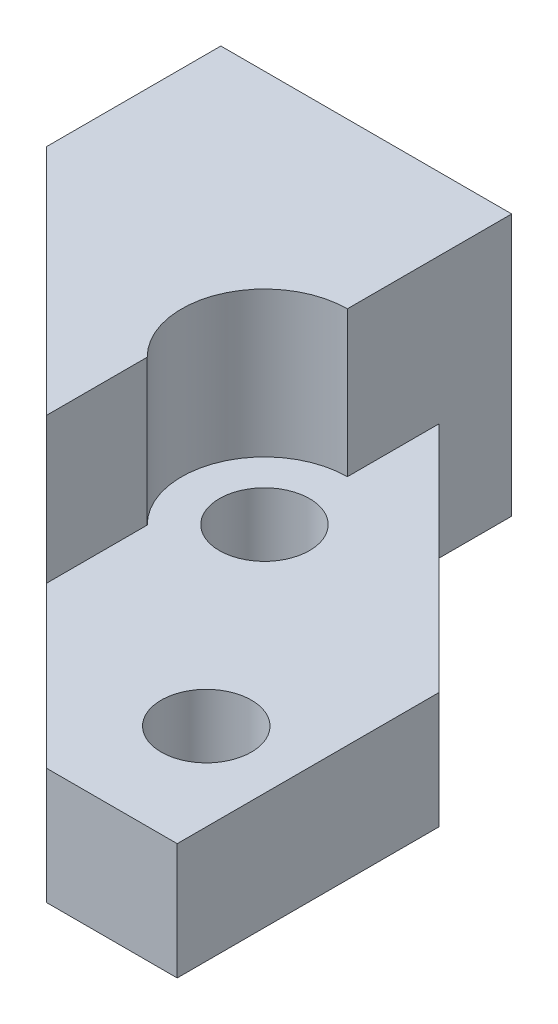
SolidWorks part; units mm, degrees
ref_plane "前视基准面" through (0, 0, 0) normal (0, 0, 1) x (1, 0, 0)
ref_plane "上视基准面" through (0, 0, 0) normal (0, 1, 0) x (1, 0, 0)
ref_plane "右视基准面" through (0, 0, 0) normal (1, 0, 0) x (0, 0, -1)
other "Configuration Table"
sketch "草图1" plane through (0, 0, 0) normal (0, 1, 0) x (1, 0, 0)
  line L1 (0, 0) -> (10, 0)
  line L2 (0, 0) -> (0, 15)
  line L3 (0, 15) -> (10, 15)
  line L4 (10, 0) -> (10, 15)
  circle A0 centre (7, 4) radius 1.55
  circle A1 centre (2, 11) radius 1.55
  dimension "D3" = 7
  dimension "D4" = 5
  dimension "D5" = 3.1
  dimension "D6" = 3.1
  dimension "D8" = 3
  dimension "D1" = 10
  dimension "D2" = 15
  dimension "D7" = 4
extrude "凸台-拉伸1" add sketch "草图1" along normal blind 4
sketch "草图2" plane through (0, 0, 0) normal (-1, 0, 0) x (0, 0, 1)
  line L1 (-5, 9) -> (-19.5, 9)
  line L2 (-5, 9) -> (-5, 0)
  line L3 (-5, 0) -> (-19.5, 0)
  line L4 (-19.5, 9) -> (-19.5, 0)
  line L5 (0, 4) -> (0, 0) construction
  line L6 (-15, 0) -> (0, 0) construction
  dimension "D1" = 5
  dimension "D2" = 14.5
  dimension "D3" = 9
  dimension "D4" = 0
extrude "凸台-拉伸2" add sketch "草图2" along normal blind 6
sketch "草图3" plane through (0, 0, -19.5) normal (0, 0, -1) x (-1, 0, 0)
  line L0 (6, 0) -> (0, 0) construction
  line L2 (0, 4) -> (0, 0) construction
  circle A0 centre (2.9, 3.9) radius 3
  dimension "D1" = 6
  dimension "D2" = 3.9
  dimension "D3" = 2.9
extrude "切除-拉伸1" cut sketch "草图3" against normal blind 3
sketch "草图4" plane through (-6, 0, 0) normal (-1, 0, 0) x (0, 0, 1)
  line L0 (-19.5, 0) -> (-5, 0) construction
  line L1 (-19.5, 9) -> (-11.5, 9)
  line L2 (-19.5, 9) -> (-19.5, 0)
  line L3 (-19.5, 0) -> (-11.5, 0)
  line L4 (-11.5, 9) -> (-11.5, 0)
  dimension "D1" = 8
extrude "凸台-拉伸3" add sketch "草图4" along normal blind 2
sketch "草图5" plane through (0, 0, 0) normal (1, 0, 0) x (0, 0, -1)
  line L0 (0, 0) -> (15, 0) construction
  line L1 (19.5, 9) -> (11.5, 9)
  line L2 (19.5, 9) -> (19.5, 0)
  line L3 (19.5, 0) -> (11.5, 0)
  line L4 (11.5, 9) -> (11.5, 0)
  dimension "D1" = 8
extrude "凸台-拉伸4" add sketch "草图5" along normal blind 2
sketch "草图6" plane through (0, 0, -19.5) normal (0, 0, -1) x (-1, 0, 0)
  circle A0 centre (2.9, 3.9) radius 3.1
  dimension "D1" = 6.2
extrude "切除-拉伸2" cut sketch "草图6" against normal blind 3
sketch "草图7" plane through (0, 4, 0) normal (0, 1, 0) x (1, 0, 0)
  circle A0 centre (2, 11) radius 1.55
  arc A2 (0.5329, 11.5) -> (2, 12.55) centre (2, 11) ccw construction
  dimension "D1" = 0
extrude "切除-拉伸3" cut sketch "草图7" against normal through all
sketch "草图8" plane through (0, 4, 0) normal (0, 1, 0) x (1, 0, 0)
  circle A0 centre (2, 11) radius 2.85
  dimension "D1" = 5.7
extrude "切除-拉伸5" cut sketch "草图8" along normal through all
chamfer "倒角1" distance 2 angle 45 1 edges at (-8, 4.5, -11.5)
chamfer "倒角2" distance 6.5 angle 45 1 edges at (-6, 4.5, -5)
chamfer "倒角3" distance 5.5 angle 45 1 edges at (0, 2, 0)
chamfer "倒角4" distance 6 angle 45 1 edges at (10, 2, -15)
chamfer "倒角5" distance 2 angle 45 1 edges at (2, 2, -15)
